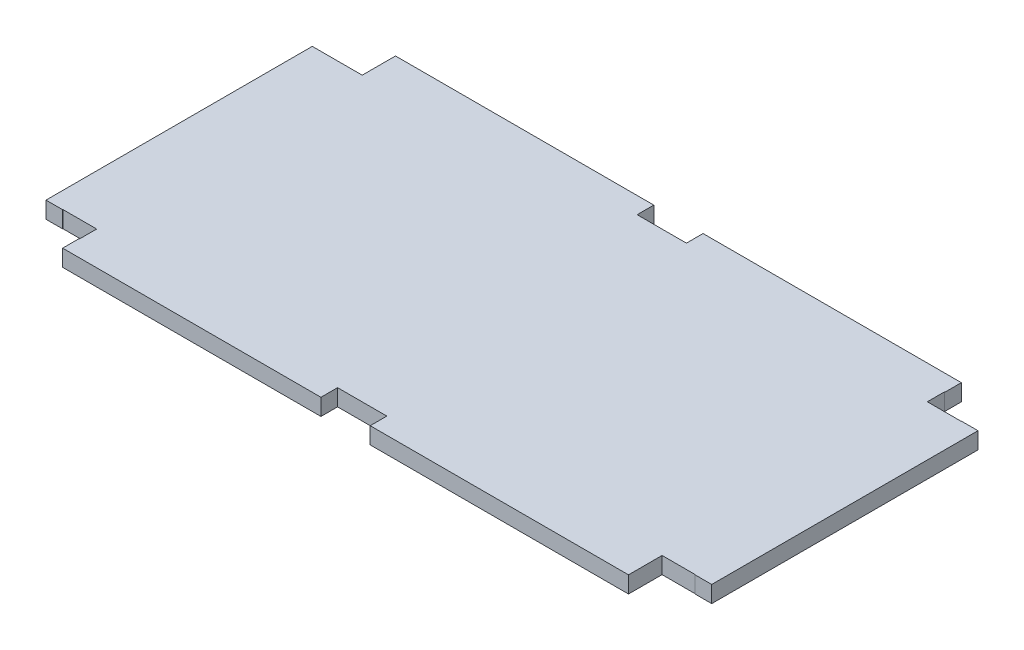
SolidWorks part; units mm, degrees
ref_plane "Front Plane" through (0, 0, 0) normal (0, 0, 1) x (1, 0, 0)
ref_plane "Top Plane" through (0, 0, 0) normal (0, 1, 0) x (1, 0, 0)
ref_plane "Right Plane" through (0, 0, 0) normal (1, 0, 0) x (0, 0, -1)
sketch "Sketch1" plane through (0, 0, 0) normal (0, 1, 0) x (1, 0, 0)
  line L1 (127, -63.5) -> (-127, -63.5)
  line L2 (127, -63.5) -> (127, 63.5)
  line L3 (127, 63.5) -> (-127, 63.5)
  line L4 (-127, -63.5) -> (-127, 63.5)
  line L5 (127, -63.5) -> (-127, 63.5) construction
  line L6 (127, 63.5) -> (-127, -63.5) construction
  point P0 (0, 0)
  dimension "D1" = 127
  dimension "D2" = 254
extrude "Boss-Extrude1" add sketch "Sketch1" along normal blind 6.35
sketch "Sketch2" plane through (0, 0, 0) normal (0, 1, 0) x (1, 0, 0)
  line L0 (-127, 0) -> (127, 0) construction
  line L1 (-127, 63.5) -> (-127, -63.5) construction
  line L2 (127, -63.5) -> (127, 63.5) construction
  line L3 (0, 63.5) -> (0, -63.5) construction
  line L4 (127, 63.5) -> (-127, 63.5) construction
  line L5 (-127, -63.5) -> (127, -63.5) construction
  line L6 (-107.95, -63.5) -> (-107.95, -57.15)
  line L7 (-127, -50.8) -> (-120.65, -50.8)
  line L8 (-9.398, -63.5) -> (-9.398, -57.15)
  line L9 (-127, 50.8) -> (-120.65, 50.8)
  line L10 (-120.65, -50.8) -> (-120.65, -57.15)
  line L11 (-120.65, -57.15) -> (-107.95, -57.15)
  line L12 (-107.95, 63.5) -> (-107.95, 57.15)
  line L13 (-120.65, 57.15) -> (-107.95, 57.15)
  line L14 (-120.65, 57.15) -> (-120.65, 50.8)
  line L15 (-9.398, 63.5) -> (-9.398, 57.15)
  line L16 (9.398, 63.5) -> (9.398, 57.15)
  line L17 (9.398, -63.5) -> (9.398, -57.15)
  line L18 (107.95, -63.5) -> (107.95, -57.15)
  line L19 (120.65, -57.15) -> (107.95, -57.15)
  line L20 (120.65, -50.8) -> (120.65, -57.15)
  line L21 (127, -50.8) -> (120.65, -50.8)
  line L22 (127, 50.8) -> (120.65, 50.8)
  line L23 (107.95, 63.5) -> (107.95, 57.15)
  line L24 (120.65, 57.15) -> (120.65, 50.8)
  line L25 (120.65, 57.15) -> (107.95, 57.15)
  line L26 (-9.398, -57.15) -> (9.398, -57.15)
  line L27 (-9.398, 57.15) -> (9.398, 57.15)
  line L28 (-127, 50.8) -> (-127, 63.5)
  line L29 (-127, 63.5) -> (-107.95, 63.5)
  line L30 (-127, -50.8) -> (-127, -63.5)
  line L31 (-127, -63.5) -> (-107.95, -63.5)
  line L32 (-9.398, 63.5) -> (9.398, 63.5)
  line L33 (-9.398, -63.5) -> (9.398, -63.5)
  line L34 (107.95, -63.5) -> (127, -63.5)
  line L35 (127, -63.5) -> (127, -50.8)
  line L36 (127, 50.8) -> (127, 63.5)
  line L37 (127, 63.5) -> (107.95, 63.5)
  dimension "D1" = 19.05
  dimension "D2" = 6.35
  dimension "D3" = 6.35
  dimension "D4" = 98.552
  dimension "D5" = 6.35
  dimension "D6" = 6.35
  dimension "D7" = 101.6
  dimension "D8" = 12.7
extrude "Cut-Extrude1" cut sketch "Sketch2" against normal blind 6.35 and the other way through all contours L29 L12 L13 L14 L9 L28 | L31 L6 L11 L10 L7 L30 | L33 L17 L26 L8 | L32 L16 L27 L15 | L37 L23 L25 L24 L22 L36 | L35 L21 L20 L19 L18 L34
sketch "Sketch3" plane through (0, 0, 0) normal (0, 1, 0) x (1, 0, 0)
  line L1 (-120.65, -57.15) -> (-107.7738, -57.15)
  line L2 (-120.65, -57.15) -> (-120.65, -50.6902)
  line L3 (-120.65, -50.6902) -> (-107.7738, -50.6902)
  line L4 (-107.7738, -57.15) -> (-107.7738, -50.6902)
  line L5 (-120.65, 50.8) -> (-107.95, 50.8)
  line L6 (-120.65, 50.8) -> (-120.65, 57.15)
  line L7 (-120.65, 57.15) -> (-107.95, 57.15)
  line L8 (-107.95, 50.8) -> (-107.95, 57.15)
  line L9 (120.65, -57.15) -> (107.95, -57.15)
  line L10 (120.65, -57.15) -> (120.65, -50.6902)
  line L11 (120.65, -50.6902) -> (107.95, -50.6902)
  line L12 (107.95, -57.15) -> (107.95, -50.6902)
  line L13 (120.65, 57.15) -> (107.95, 57.15)
  line L14 (120.65, 57.15) -> (120.65, 50.8)
  line L15 (120.65, 50.8) -> (107.95, 50.8)
  line L16 (107.95, 57.15) -> (107.95, 50.8)
extrude "Cut-Extrude3" cut sketch "Sketch3" against normal blind 127 and the other way blind 127 contours L2 L1 L4 L3 | L10 L9 L12 L11 | L6 L5 L8 L7
sketch "Sketch4" plane through (0, 0, 0) normal (0, -1, 0) x (-1, 0, 0)
  line L1 (-120.65, 57.15) -> (-107.7738, 57.15)
  line L2 (-120.65, 57.15) -> (-120.65, 50.6902)
  line L3 (-120.65, 50.6902) -> (-107.7738, 50.6902)
  line L4 (-107.7738, 57.15) -> (-107.7738, 50.6902)
extrude "Cut-Extrude4" cut sketch "Sketch4" against normal blind 127 and the other way blind 127
